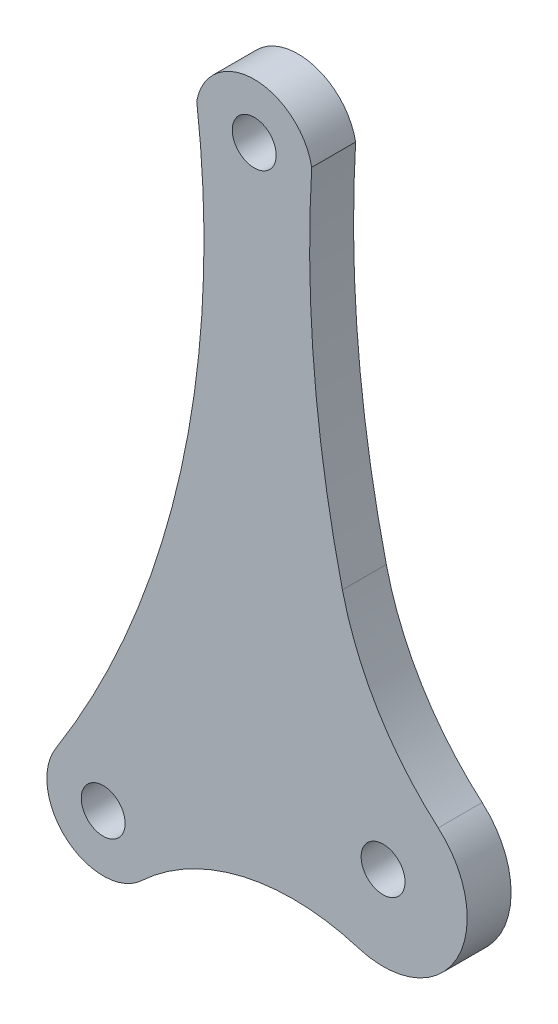
SolidWorks part; units mm, degrees
ref_plane "Plan de face" through (0, 0, 0) normal (0, 0, 1) x (1, 0, 0)
ref_plane "Plan de dessus" through (0, 0, 0) normal (0, 1, 0) x (1, 0, 0)
ref_plane "Plan de droite" through (0, 0, 0) normal (1, 0, 0) x (0, 0, -1)
sketch "Esquisse1" plane through (0, 0, 0) normal (0, 0, 1) x (1, 0, 0)
  line L0 (1270.9726, 1456.9058) -> (1270.5885, 1404.4072) construction
  circle A0 centre (1279.6599, 1414.5286) radius 1.5
  circle A1 centre (1260.5343, 1408.429) radius 1.5
  circle A2 centre (1270.8553, 1453.1379) radius 1.5
  arc A3 (1266.925, 1453.6371) -> (1274.7827, 1453.6371) centre (1270.8539, 1452.8858) cw
  arc A4 (1274.7827, 1453.6371) -> (1276.8823, 1429.684) centre (1357.4896, 1448.8184) ccw
  arc A5 (1266.925, 1453.6371) -> (1257.2788, 1410.4843) centre (1201.7234, 1445.5575) cw
  arc A6 (1257.2788, 1410.4843) -> (1263.1664, 1405.6192) centre (1260.5343, 1408.429) ccw
  arc A7 (1277.9651, 1409.034) -> (1283.4297, 1418.8704) centre (1279.6599, 1414.5286) ccw
  arc A8 (1276.8823, 1429.684) -> (1283.4297, 1418.8704) centre (1296.9558, 1434.449) ccw
  arc A9 (1263.1664, 1405.6192) -> (1277.9651, 1409.034) centre (1273.507, 1394.5803) cw
  dimension "D2" = 3
  dimension "D3" = 3
  dimension "D4" = 3
  dimension "D5" = 4
  dimension "D6" = 7.7
  dimension "D7" = 11.5
  dimension "D1" = 52.5
base flange "Tôle de base pliée1" sketch "Esquisse1" thickness 3 reverse thickness direction no parameters "D1"=1.5
sketch "Lignes de pliage1" [suppressed] plane through (0, 0, 0) normal (0, 1, 0) x (1, 0, 0)
sketch "Cube de visualisation1" [suppressed] plane through (0, 0, 0) normal (0, 1, 0) x (1, 0, 0)
sheet metal parameters "Tôlerie1" thickness 3 parameters "D1"=1.5
flat pattern "Etat déplié1" [suppressed]
sketch "Lignes de pliage2" plane through (0, 0, 0) normal (0, 1, 0) x (1, 0, 0)
sketch3d "Cube de visualisation2" [suppressed]
  line L0 (51.0023, -27.4517, 0) -> (62.9254, 24.6906, 0) construction
  line L1 (24.7942, -21.4589, 0) -> (36.7173, 30.6835, 0) construction
  line L2 (51.0023, -27.4517, 0) -> (24.7942, -21.4589, 0) construction
  line L3 (62.9254, 24.6906, 0) -> (36.7173, 30.6835, 0) construction
